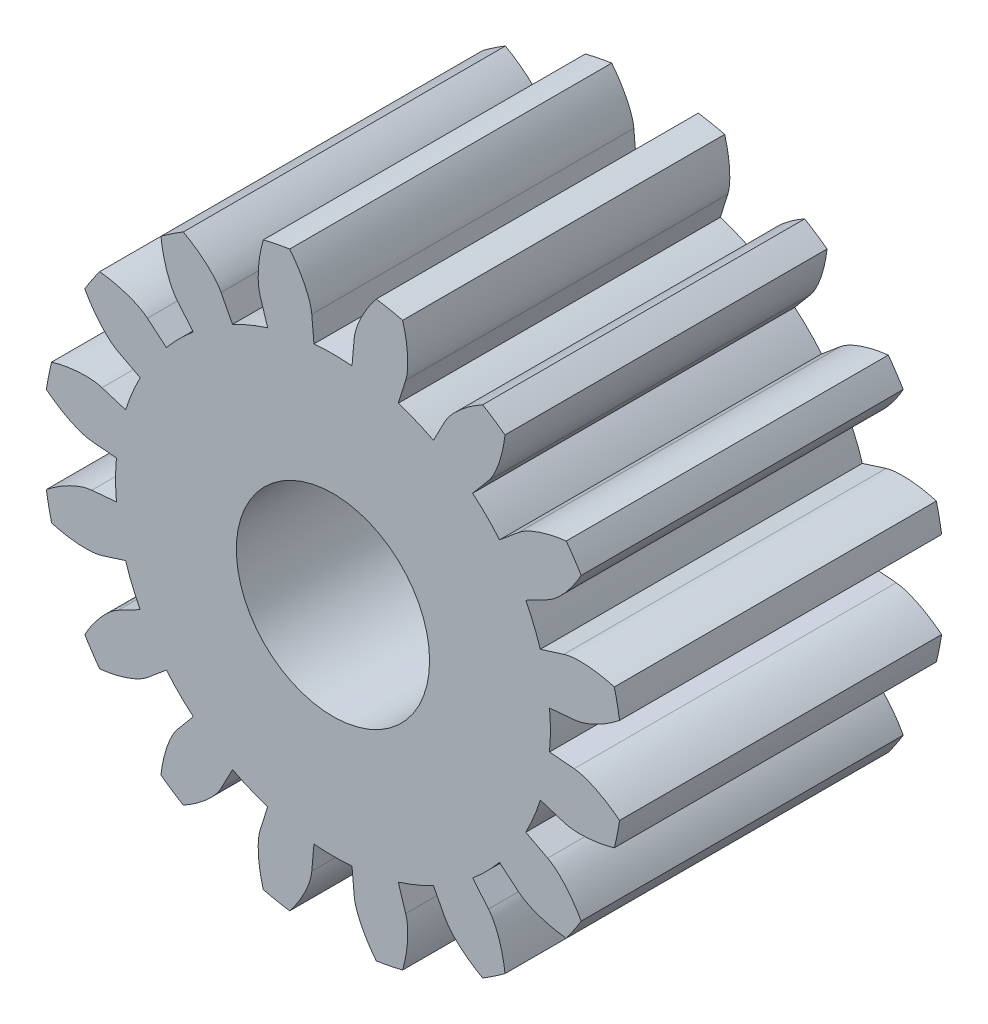
SolidWorks part; units mm, degrees
ref_plane "前视基准面" through (0, 0, 0) normal (0, 0, 1) x (1, 0, 0)
ref_plane "上视基准面" through (0, 0, 0) normal (0, 1, 0) x (1, 0, 0)
ref_plane "右视基准面" through (0, 0, 0) normal (1, 0, 0) x (0, 0, -1)
other "Configuration Table"
sketch "草图1" plane through (0, 0, 0) normal (0, 0, 1) x (1, 0, 0)
  line L0 (0, 0) -> (4, 0) construction
  line L1 (0, 0) -> (3.9807, 0.3921) construction
  line L2 (0, 0) -> (3.7443, 0.3291)
  line L3 (3.9807, 0.3921) -> (3.9807, -0.3921) construction
  line L4 (0, 0) -> (3.7443, -0.3291)
  circle A0 centre (0, 0) radius 4.5
  circle A1 centre (0, 0) radius 4 construction
  circle A2 centre (0, 0) radius 3.375
  circle A3 centre (0, 0) radius 3.7588 construction
  circle A4 centre (0, 0) radius 1.5
  spline S0 degree 4 poles (3.7443, 0.3291) (3.7729, 0.3316) (3.852, 0.3445) (3.9981, 0.3926) (4.2218, 0.5023) (4.4866, 0.6881) (4.7894, 0.9723) (5.0903, 1.3552) (5.3572, 1.8186) (5.6269, 2.4866) (5.7837, 3.1915) (5.8395, 3.939) (5.7839, 4.8292) (5.6145, 5.7064) (5.2709, 6.6864) (4.7256, 7.7028) (4.0402, 8.6299) (3.2362, 9.4556) (2.3338, 10.1718) (1.3511, 10.7732) (0.306, 11.2565) (-0.6502, 11.5751) (-1.4192, 11.7574) (-1.9866, 11.8556) (-2.3401, 11.9048) (-2.6306, 11.9368) (-2.9071, 11.9619) (-3.2112, 11.9792) (-3.4455, 11.9894) (-3.715, 11.9923) (-3.9867, 11.9914) (-4.2588, 11.9836) (-4.7357, 11.9589) (-5.1232, 11.9154) (-5.525, 11.8674) (-5.7188, 11.8311) (-5.8484, 11.8109) knots 0 0 0 0 0 0.005604 0.015718 0.02996 0.048734 0.068727 0.096889 0.125051 0.153212 0.209535 0.237696 0.271429 0.327752 0.384075 0.440398 0.496721 0.553044 0.609367 0.66569 0.722013 0.778336 0.806497 0.820578 0.834659 0.84874 0.86282 0.876901 0.890982 0.900036 0.909091 0.931818 0.954545 0.977273 1 1 1 1 1 construction
  spline S1 degree 4 poles (3.7443, 0.3291) (3.7729, 0.3316) (3.852, 0.3445) (3.9981, 0.3926) (4.2218, 0.5023) (4.4866, 0.6881) (4.7894, 0.9723) (5.0903, 1.3552) (5.3572, 1.8186) (5.6269, 2.4866) (5.7837, 3.1915) (5.8395, 3.939) (5.7839, 4.8292) (5.6145, 5.7064) (5.2709, 6.6864) (4.7256, 7.7028) (4.0402, 8.6299) (3.2362, 9.4556) (2.3338, 10.1718) (1.3511, 10.7732) (0.306, 11.2565) (-0.6502, 11.5751) (-1.4192, 11.7574) (-1.9866, 11.8556) (-2.3401, 11.9048) (-2.6306, 11.9368) (-2.9071, 11.9619) (-3.2112, 11.9792) (-3.4455, 11.9894) (-3.715, 11.9923) (-3.8743, 11.9918) (-3.9585, 11.9906) (-4.0005, 11.9898) knots 0 0 0 0 0 0.005604 0.015718 0.02996 0.048734 0.068727 0.096889 0.125051 0.153212 0.209535 0.237696 0.271429 0.327752 0.384075 0.440398 0.496721 0.553044 0.609367 0.66569 0.722013 0.778336 0.806497 0.820578 0.834659 0.84874 0.86282 0.876901 0.890982 0.900036 0.909091 0.909091 0.909091 0.909091 0.909091
  spline S2 degree 4 poles (3.7443, -0.3291) (3.7729, -0.3316) (3.852, -0.3445) (3.9981, -0.3926) (4.2218, -0.5023) (4.4866, -0.6881) (4.7894, -0.9723) (5.0903, -1.3552) (5.3572, -1.8186) (5.6269, -2.4866) (5.7837, -3.1915) (5.8395, -3.939) (5.7839, -4.8292) (5.6145, -5.7064) (5.2709, -6.6864) (4.7256, -7.7028) (4.0402, -8.6299) (3.2362, -9.4556) (2.3338, -10.1718) (1.3511, -10.7732) (0.306, -11.2565) (-0.6502, -11.5751) (-1.4192, -11.7574) (-1.9866, -11.8556) (-2.3401, -11.9048) (-2.6306, -11.9368) (-2.9071, -11.9619) (-3.2112, -11.9792) (-3.4455, -11.9894) (-3.715, -11.9923) (-3.9867, -11.9914) (-4.2588, -11.9836) (-4.7357, -11.9589) (-5.1232, -11.9154) (-5.525, -11.8674) (-5.7188, -11.8311) (-5.8484, -11.8109) knots 0 0 0 0 0 0.005604 0.015718 0.02996 0.048734 0.068727 0.096889 0.125051 0.153212 0.209535 0.237696 0.271429 0.327752 0.384075 0.440398 0.496721 0.553044 0.609367 0.66569 0.722013 0.778336 0.806497 0.820578 0.834659 0.84874 0.86282 0.876901 0.890982 0.900036 0.909091 0.931818 0.954545 0.977273 1 1 1 1 1 construction
  spline S3 degree 4 poles (3.7443, -0.3291) (3.7729, -0.3316) (3.852, -0.3445) (3.9981, -0.3926) (4.2218, -0.5023) (4.4866, -0.6881) (4.7894, -0.9723) (5.0903, -1.3552) (5.3572, -1.8186) (5.6269, -2.4866) (5.7837, -3.1915) (5.8395, -3.939) (5.7839, -4.8292) (5.6145, -5.7064) (5.2709, -6.6864) (4.7256, -7.7028) (4.0402, -8.6299) (3.2362, -9.4556) (2.3338, -10.1718) (1.3511, -10.7732) (0.306, -11.2565) (-0.6502, -11.5751) (-1.4192, -11.7574) (-1.9866, -11.8556) (-2.3401, -11.9048) (-2.6306, -11.9368) (-2.9071, -11.9619) (-3.2112, -11.9792) (-3.4455, -11.9894) (-3.715, -11.9923) (-3.8743, -11.9918) (-3.9585, -11.9906) (-4.0005, -11.9898) knots 0 0 0 0 0 0.005604 0.015718 0.02996 0.048734 0.068727 0.096889 0.125051 0.153212 0.209535 0.237696 0.271429 0.327752 0.384075 0.440398 0.496721 0.553044 0.609367 0.66569 0.722013 0.778336 0.806497 0.820578 0.834659 0.84874 0.86282 0.876901 0.890982 0.900036 0.909091 0.909091 0.909091 0.909091 0.909091
  point P15 (3.9807, 0)
  dimension "齿顶圆直径" = 9
  dimension "分度圆直径" = 8
  dimension "齿根圆直径" = 6.75
  dimension "基圆直径" = 7.5175
  dimension "内孔直径" = 3
  dimension "渐近线镜像线夹角" = 5.625
extrude "凸台-拉伸1" add sketch "草图1" along normal blind 5 contours A0 | A4
extrude "切除-拉伸1" cut sketch "草图1<3>" along normal through all contours A2 S3 A0 S1 region at (4.0116, 0, 0)
sketch "草图1<3>" plane through (0, 0, 0) normal (0, 0, 1) x (1, 0, 0) same geometry as "草图1"
pattern_circular "阵列(圆周)1" count 16 every 22.5 about axis through (0, 0, 5) along (0, 0, 1) of "切除-拉伸1"
equation "\"m\"= 0.5'模数"
equation "\"z\"= 16'齿数"
equation "\"a\"= 20度'压力角"
equation "\"d\"= \"m\" * \"z\"'分度圆直径"
equation "\"da\"= ( \"z\" + 2 ) * \"m\"'齿顶圆直径"
equation "\"df\"= ( \"z\" - 2.5 ) * \"m\"'齿根圆直径"
equation "\"s\"= 0.5 * PI * \"m\"'分度圆齿厚"
equation "\"r\"= 0.38 * \"m\"'齿根圆角"
equation "\"B\"= 0.3 * \"d\"'齿厚"
equation "\"db\"= \"m\" * \"z\" * cos ( \"a\" )'基圆直径"
equation "\"rb\"= \"db\" / 2'基圆半径"
equation "\"齿顶圆直径@草图1\"= \"da\""
equation "\"分度圆直径@草图1\"= \"d\""
equation "\"齿根圆直径@草图1\"= \"df\""
equation "\"基圆直径@草图1\"= \"db\""
equation "\"渐近线镜像线夹角@草图1\"= 360 / 4 / \"z\""
equation "\"h\"= 5'齿轮厚度"
equation "\"ir\"= 3'内孔直径"
equation "\"内孔直径@草图1\"= \"ir\""
equation "\"齿轮厚@凸台-拉伸1\"= \"h\""
equation "\"齿轮夹角@阵列(圆周)1\"= 360 / \"z\""
equation "\"齿数@阵列(圆周)1\"= \"z\""
